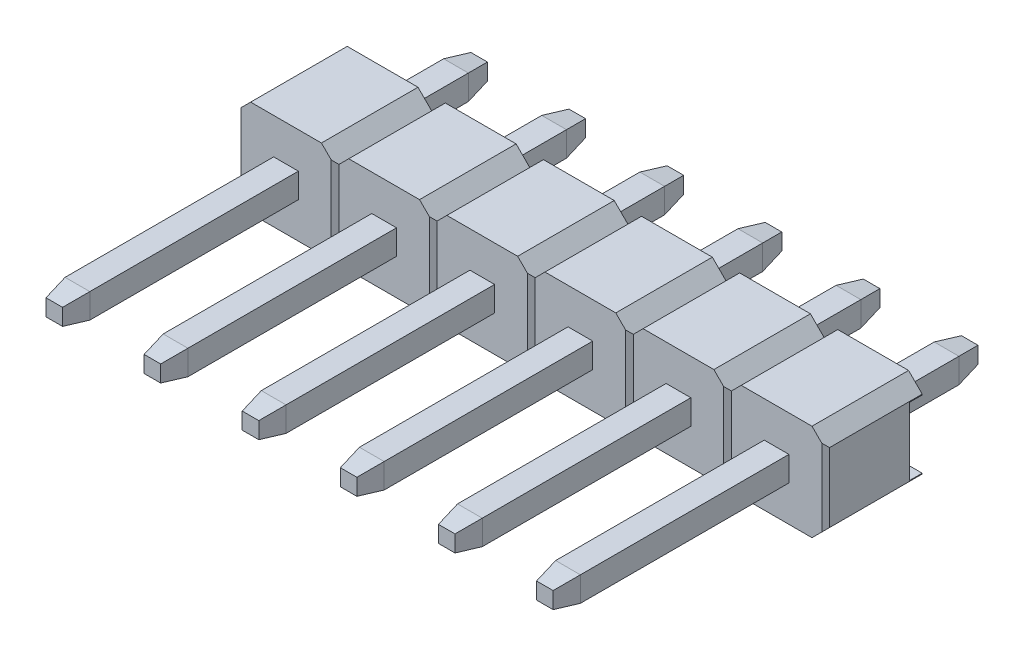
SolidWorks part; units mm, degrees
ref_plane "Front Plane" through (0, 0, 0) normal (0, 0, 1) x (1, 0, 0)
ref_plane "Top Plane" through (0, 0, 0) normal (0, 1, 0) x (1, 0, 0)
ref_plane "Right Plane" through (0, 0, 0) normal (1, 0, 0) x (0, 0, -1)
sketch "Sketch1" plane through (0, 0, 0) normal (0, 0, 1) x (1, 0, 0)
  line L0 (-1.27, 0.8964) -> (-0.9164, 1.25)
  line L1 (-0.9164, 1.25) -> (0.9164, 1.25)
  line L2 (-1.27, 0.8964) -> (-1.27, -0.8964)
  line L3 (-0.9164, -1.25) -> (0.9164, -1.25)
  line L4 (1.27, 0.8964) -> (1.27, -0.8964)
  line L5 (-1.27, -0.8964) -> (-0.9164, -1.25)
  line L6 (0.9164, -1.25) -> (1.27, -0.8964)
  line L7 (1.27, 0.8964) -> (0.9164, 1.25)
  point P0 (1.27, -1.25)
  point P7 (-1.27, 1.25)
  point P10 (-1.27, -1.25)
  point P15 (1.27, 1.25)
  dimension "D5" = 0.25
  dimension "D1" = 2.54
  dimension "D2" = 2.5
  dimension "D3" = 1.27
  dimension "D4" = 1.25
  dimension "D6" = 0.25
  dimension "D7" = 0.25
  dimension "D8" = 0.25
extrude "Extrude1" add sketch "Sketch1" along normal blind 1.25 and the other way blind 1.25
sketch "Sketch4" plane through (0, 0, 0) normal (0, 1, 0) x (1, 0, 0)
  line L0 (-1.27, -1.15) -> (-1.17, -1.25)
  line L1 (-1.17, -1.25) -> (-1.27, -1.25)
  line L2 (-1.27, -1.25) -> (-1.27, -1.15)
  line L3 (1.17, -1.25) -> (1.27, -1.15)
  line L4 (1.27, -1.15) -> (1.27, -1.25)
  line L5 (1.27, -1.25) -> (1.17, -1.25)
extrude "Cut-Extrude3" cut sketch "Sketch4" against normal through all and the other way through all
pattern_linear "LPattern4" count 6 spacing 2.54 along (-1, 0, 0) of "Extrude1", "Cut-Extrude3"
sketch "Sketch2" plane through (0, 0, 0) normal (1, 0, 0) x (0, -1, 0)
  line L1 (-0.8764, 1.25) -> (0.8764, 1.25)
  line L2 (-0.8764, 1.25) -> (-0.8764, 0.92)
  line L3 (-0.8764, 0.92) -> (0.8764, 0.92)
  line L4 (0.8764, 1.25) -> (0.8764, 0.92)
  dimension "D1" = 0.33
extrude "Cut-Extrude1" cut sketch "Sketch2" against normal through all and the other way through all
sketch "Sketch3" plane through (0, 0, 0) normal (1, 0, 0) x (0, 0, -1)
  line L0 (-7.25, 0) -> (3.75, 0)
  line L1 (1.25, 1.25) -> (1.25, 0.8964) construction
  dimension "D1" = 6
  dimension "D2" = 2.5
extrude "Extrude-Thin1" add sketch "Sketch3" along normal blind 0.32 and the other way blind 0.32 thin thin type mid plane wall 0.64
pattern_linear "LPattern5" count 1 spacing 2.54 along (1, 0, 0) count 6 spacing 2.54 along (-1, 0, 0) of "Extrude-Thin1"
chamfer "Chamfer2" distance 0.6 angle 10 48 edges at (0.32, 0, 7.25) (0, -0.32, 7.25) (-0.32, 0, 7.25) (0, 0.32, 7.25) (0.32, 0, -3.75) (-0.32, 0, -3.75) (-4.76, 0, -3.75) (-5.4, 0, -3.75) (-2.22, 0, -3.75) (-2.86, 0, -3.75) (-2.22, 0, 7.25) (-2.54, -0.32, 7.25) (-2.86, 0, 7.25) (-2.54, 0.32, 7.25) (-4.76, 0, 7.25) (-5.08, -0.32, 7.25) (-5.4, 0, 7.25) (-5.08, 0.32, 7.25) (-2.54, 0.32, -3.75) (-2.54, -0.32, -3.75) (0, 0.32, -3.75) (0, -0.32, -3.75) (-9.84, 0, -3.75) (-10.16, 0.32, -3.75) (-10.48, 0, -3.75) (-10.16, -0.32, -3.75) (-7.3, 0, -3.75) (-7.62, 0.32, -3.75) (-7.94, 0, -3.75) (-7.62, -0.32, -3.75) (-5.08, 0.32, -3.75) (-5.08, -0.32, -3.75) (-9.84, 0, 7.25) (-10.16, -0.32, 7.25) (-10.48, 0, 7.25) (-10.16, 0.32, 7.25) (-7.3, 0, 7.25) (-7.62, -0.32, 7.25) (-7.94, 0, 7.25) (-7.62, 0.32, 7.25) (-12.38, 0, -3.75) (-12.7, 0.32, -3.75) (-13.02, 0, -3.75) (-12.7, -0.32, -3.75) (-12.38, 0, 7.25) (-12.7, -0.32, 7.25) (-13.02, 0, 7.25) (-12.7, 0.32, 7.25) first distance on face at (0.32, 0, 4.25) first distance on face at (0, -0.32, 4.25) first distance on face at (-0.32, 0, 4.25) first distance on face at (0, 0.32, 4.25) first distance on face at (0.32, 0, -2.335) first distance on face at (-0.32, 0, -2.335) first distance on face at (-4.76, 0, -2.335) first distance on face at (-5.4, 0, -2.335) first distance on face at (-2.22, 0, -2.335) first distance on face at (-2.86, 0, -2.335) first distance on face at (-2.22, 0, 4.25) first distance on face at (-2.54, -0.32, 4.25) first distance on face at (-2.86, 0, 4.25) first distance on face at (-2.54, 0.32, 4.25) first distance on face at (-4.76, 0, 4.25) first distance on face at (-5.08, -0.32, 4.25) first distance on face at (-5.4, 0, 4.25) first distance on face at (-5.08, 0.32, 4.25) first distance on face at (-2.54, 0.32, -2.335) first distance on face at (-2.54, -0.32, -2.335) first distance on face at (0, 0.32, -2.335) first distance on face at (0, -0.32, -2.335) first distance on face at (-9.84, 0, -2.335) first distance on face at (-10.16, 0.32, -2.335) first distance on face at (-10.48, 0, -2.335) first distance on face at (-10.16, -0.32, -2.335) first distance on face at (-7.3, 0, -2.335) first distance on face at (-7.62, 0.32, -2.335) first distance on face at (-7.94, 0, -2.335) first distance on face at (-7.62, -0.32, -2.335) first distance on face at (-5.08, 0.32, -2.335) first distance on face at (-5.08, -0.32, -2.335) first distance on face at (-9.84, 0, 4.25) first distance on face at (-10.16, -0.32, 4.25) first distance on face at (-10.48, 0, 4.25) first distance on face at (-10.16, 0.32, 4.25) first distance on face at (-7.3, 0, 4.25) first distance on face at (-7.62, -0.32, 4.25) first distance on face at (-7.94, 0, 4.25) first distance on face at (-7.62, 0.32, 4.25) first distance on face at (-12.38, 0, -2.335) first distance on face at (-12.7, 0.32, -2.335) first distance on face at (-13.02, 0, -2.335) first distance on face at (-12.7, -0.32, -2.335) first distance on face at (-12.38, 0, 4.25) first distance on face at (-12.7, -0.32, 4.25) first distance on face at (-13.02, 0, 4.25) first distance on face at (-12.7, 0.32, 4.25)
ref_plane "Board Plane" through (0, 0, -1.5) normal (0, 0, 1) x (1, 0, 0)
sketch "Component_Outline" plane through (0, 0, -1.5) normal (0, 0, 1) x (1, 0, 0)
  line L0 (1.27, 0.8964) -> (1.27, -0.8964)
  line L1 (1.27, -0.8964) -> (0.9164, -1.25)
  line L2 (0.9164, -1.25) -> (-0.9164, -1.25)
  line L3 (-0.9164, -1.25) -> (-1.27, -0.8964)
  line L4 (-1.27, -0.8964) -> (-1.6236, -1.25)
  line L5 (-1.6236, -1.25) -> (-3.4564, -1.25)
  line L6 (-3.4564, -1.25) -> (-3.81, -0.8964)
  line L7 (-3.81, -0.8964) -> (-4.1636, -1.25)
  line L8 (-4.1636, -1.25) -> (-5.9964, -1.25)
  line L9 (-5.9964, -1.25) -> (-6.35, -0.8964)
  line L10 (-6.35, -0.8964) -> (-6.7036, -1.25)
  line L11 (-6.7036, -1.25) -> (-8.5364, -1.25)
  line L12 (-8.5364, -1.25) -> (-8.89, -0.8964)
  line L13 (-8.89, -0.8964) -> (-9.2436, -1.25)
  line L14 (-9.2436, -1.25) -> (-11.0764, -1.25)
  line L15 (-11.0764, -1.25) -> (-11.43, -0.8964)
  line L17 (-11.43, 0.8964) -> (-11.0764, 1.25)
  line L18 (-11.0764, 1.25) -> (-9.2436, 1.25)
  line L19 (-9.2436, 1.25) -> (-8.89, 0.8964)
  line L20 (-8.89, 0.8964) -> (-8.5364, 1.25)
  line L21 (-8.5364, 1.25) -> (-6.7036, 1.25)
  line L22 (-6.7036, 1.25) -> (-6.35, 0.8964)
  line L23 (-6.35, 0.8964) -> (-5.9964, 1.25)
  line L24 (-5.9964, 1.25) -> (-4.1636, 1.25)
  line L25 (-4.1636, 1.25) -> (-3.81, 0.8964)
  line L26 (-3.81, 0.8964) -> (-3.4564, 1.25)
  line L27 (-3.4564, 1.25) -> (-1.6236, 1.25)
  line L28 (-1.6236, 1.25) -> (-1.27, 0.8964)
  line L29 (-1.27, 0.8964) -> (-0.9164, 1.25)
  line L30 (-0.9164, 1.25) -> (0.9164, 1.25)
  line L31 (0.9164, 1.25) -> (1.27, 0.8964)
  line L32 (-11.43, 0.8964) -> (-11.7836, 1.25)
  line L33 (-11.7836, 1.25) -> (-13.6564, 1.25)
  line L34 (-13.6564, 1.25) -> (-13.97, 0.9364)
  line L35 (-13.97, 0.9364) -> (-13.97, -0.8964)
  line L36 (-13.97, -0.8964) -> (-13.6164, -1.25)
  line L37 (-13.6164, -1.25) -> (-11.7836, -1.25)
  line L38 (-11.7836, -1.25) -> (-11.43, -0.8964)
  point P64 (0, 0)
